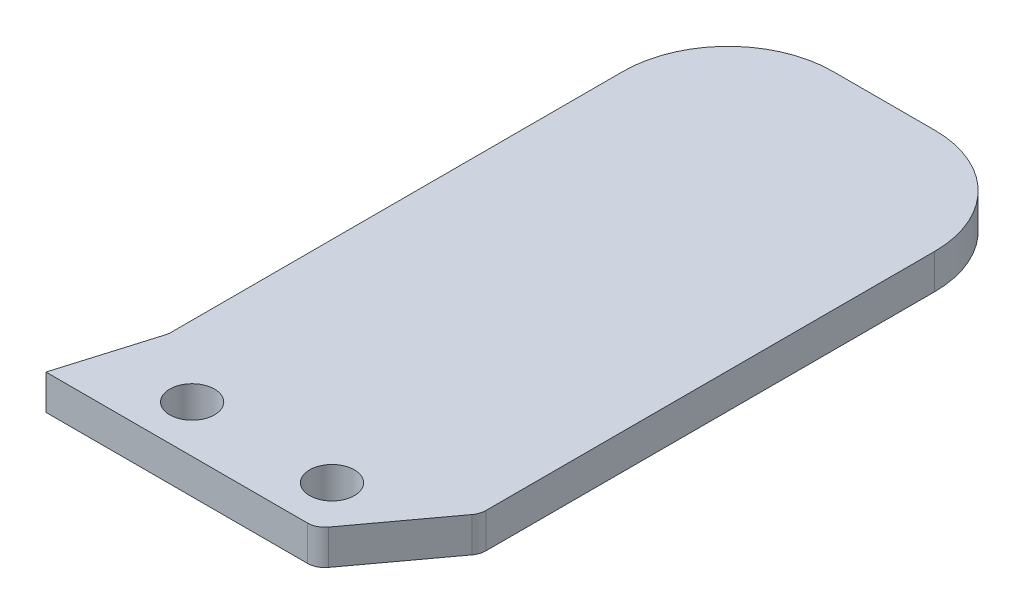
SolidWorks part; units mm, degrees
ref_plane "Front Plane" through (0, 0, 0) normal (0, 0, 1) x (1, 0, 0)
ref_plane "Top Plane" through (0, 0, 0) normal (0, 1, 0) x (1, 0, 0)
ref_plane "Right Plane" through (0, 0, 0) normal (1, 0, 0) x (0, 0, -1)
sketch "Sketch1" plane through (0, 0, 0) normal (0, 1, 0) x (1, 0, 0)
  line L9 (0, 0) -> (2.557, 8.5605)
  line L10 (0, 0) -> (24.5427, 0)
  line L14 (2.557, 8.5605) -> (2.557, 59.3605)
  line L15 (24.5427, 0) -> (30.8535, 8.5605)
  line L16 (30.8535, 8.5605) -> (30.8535, 59.3605)
  line L17 (30.8535, 59.3605) -> (2.557, 59.3605)
  circle A0 centre (8.9852, 4.2803) radius 2.032
  circle A1 centre (21.6852, 4.2803) radius 2.032
  point P18 (22.8971, 0)
  point P19 (35.9371, 0)
  point P20 (4.2548, 8.5605)
  point P21 (2.6145, 8.5605)
  point P23 (24.3624, 0)
  point P25 (29.6726, 8.5605)
  dimension "D2" = 4.064
  dimension "D1" = 50.8
extrude "Boss-Extrude1" add sketch "Sketch1" along normal blind 3.175
fillet "Fillet1" radius 9.525 2 edges at (2.557, 1.5875, -59.3605) (30.8535, 1.5875, -59.3605)
fillet "Fillet2" radius 1.5875 3 edges at (2.557, 1.5875, -8.5605) (30.8535, 1.5875, -8.5605) (24.5427, 1.5875, 0)
